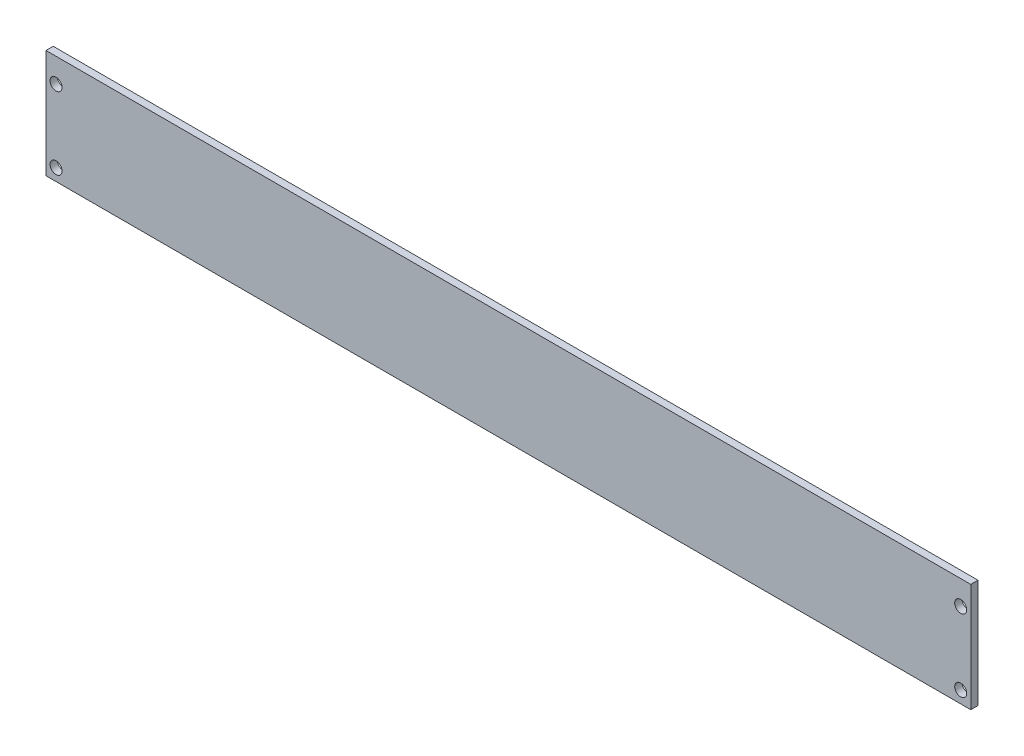
SolidWorks part; units mm, degrees
material "AISI 4130 Steel, normalized at 870C"
ref_plane "Front Plane" through (0, 0, 0) normal (0, 0, 1) x (1, 0, 0)
ref_plane "Top Plane" through (0, 0, 0) normal (0, 1, 0) x (1, 0, 0)
ref_plane "Right Plane" through (0, 0, 0) normal (1, 0, 0) x (0, 0, -1)
sketch "Sketch1" plane through (0, 0, 0) normal (0, 0, 1) x (1, 0, 0)
  line L0 (-142.875, 9.525) -> (-142.875, -13.335) construction
  line L1 (146.05, 17.145) -> (-146.05, 17.145)
  line L2 (146.05, 17.145) -> (146.05, -17.145)
  line L3 (146.05, -17.145) -> (-146.05, -17.145)
  line L4 (-146.05, 17.145) -> (-146.05, -17.145)
  line L5 (146.05, 17.145) -> (-146.05, -17.145) construction
  line L6 (146.05, -17.145) -> (-146.05, 17.145) construction
  line L7 (-142.875, 9.525) -> (142.875, 9.525) construction
  circle A2 centre (-142.875, 9.525) radius 1.8987
  circle A3 centre (-142.875, -13.335) radius 1.8987
  circle A4 centre (142.875, 9.525) radius 1.8987
  circle A5 centre (142.875, -13.335) radius 1.8987
  point P0 (0, 0)
  point P8 (-142.875, -1.905)
  point P15 (0, 9.525)
  dimension "D3" = 3.175
  dimension "D4" = 3.7973
  dimension "D1" = 34.29
  dimension "D2" = 292.1
  dimension "D5" = 7.62
  dimension "D6" = 30.48
extrude "Boss-Extrude1" add sketch "Sketch1" along normal blind 2.286
